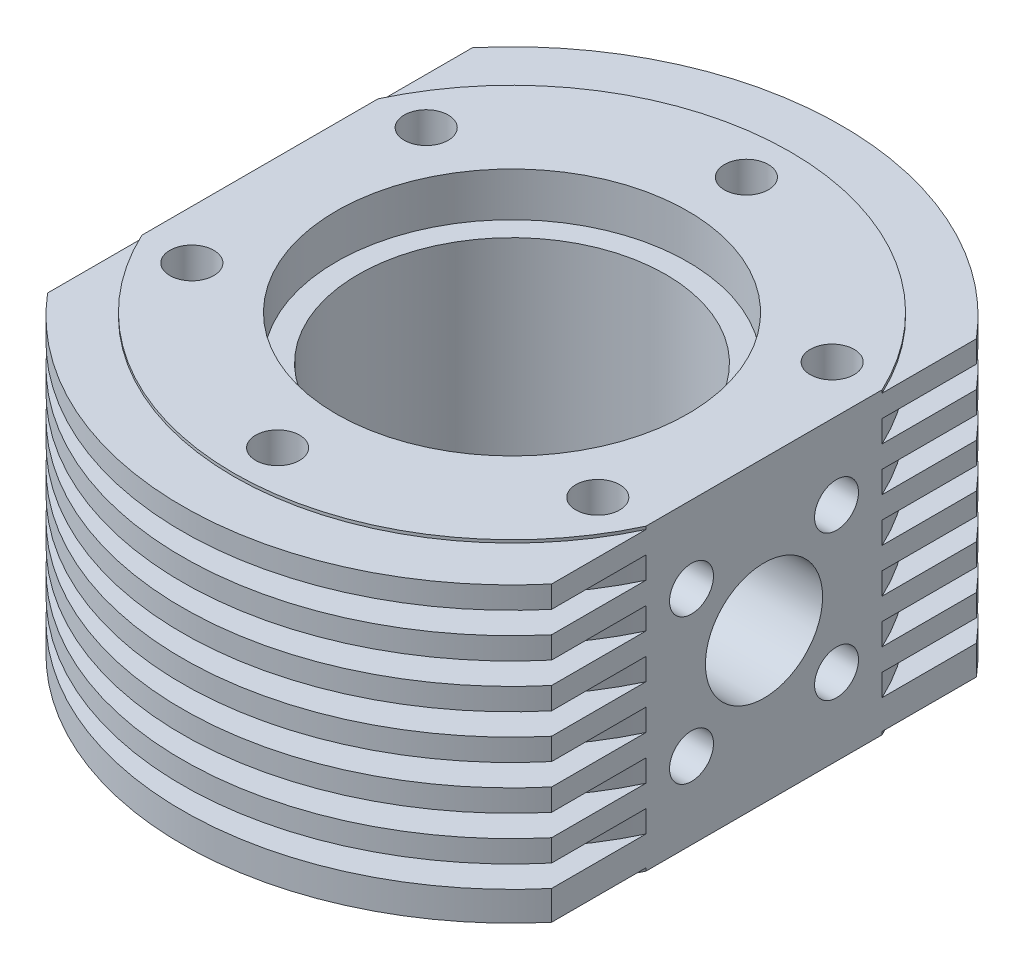
SolidWorks part; units mm, degrees
ref_plane "Front Plane" through (0, 0, 0) normal (0, 0, 1) x (1, 0, 0)
ref_plane "Top Plane" through (0, 0, 0) normal (0, 1, 0) x (1, 0, 0)
ref_plane "Right Plane" through (0, 0, 0) normal (1, 0, 0) x (0, 0, -1)
sketch "Sketch1" plane through (0, 0, 0) normal (0, 1, 0) x (1, 0, 0)
  line L0 (-17.2047, 14.5) -> (-17.2047, -14.5)
  line L1 (0, 0) -> (0, 11.2586) construction
  line L2 (17.2047, 14.5) -> (17.2047, -14.5)
  arc A0 (-17.2047, -14.5) -> (17.2047, -14.5) centre (0, 0) ccw
  arc A1 (-17.2047, -8.0623) -> (17.2047, -8.0623) centre (0, 0) ccw
  circle A2 centre (0, 0) radius 16 construction
  circle A3 centre (0, 16) radius 1.5
  circle A4 centre (13.8564, 8) radius 1.5
  circle A5 centre (13.8564, -8) radius 1.5
  circle A6 centre (0, -16) radius 1.5
  circle A7 centre (-13.8564, -8) radius 1.5
  circle A8 centre (-13.8564, 8) radius 1.5
  arc A9 (17.2047, 8.0623) -> (-17.2047, 8.0623) centre (0, 0) ccw
  arc A10 (17.2047, 14.5) -> (-17.2047, 14.5) centre (0, 0) ccw
  point P19 (0, 0)
  dimension "D1" = 45
  dimension "D2" = 38
  dimension "D3" = 32
  dimension "D4" = 3
  dimension "D5" = 6
extrude "Boss-Extrude1" add sketch "Sketch1" along normal mid plane 20 contours L2 A10 L0 A9 | A1 L0 A0 L2 region at (0, 0, -22.1268) region at (0, 0, 19.3732)
extrude "Boss-Extrude2" add sketch "Sketch1<4>" along normal mid plane 20.4 contours L2 A9 L0 A1 A3 A4 A5 A6 A7 A8 region at (0, 0, 0)
sketch "Sketch1<4>" plane through (0, 0, 0) normal (0, 1, 0) x (1, 0, 0) same geometry as "Sketch1"
sketch "Sketch2" plane through (0, 10.2, 0) normal (0, 1, 0) x (1, 0, 0)
  circle A0 centre (0, 0) radius 12
  circle A1 centre (0, 0) radius 10.5
  dimension "D1" = 24
  dimension "D2" = 21
extrude "Cut-Extrude1" cut sketch "Sketch2" against normal through all contours A1 region at (0, 10.2, 0)
extrude "Cut-Extrude2" cut sketch "Sketch2<3>" against normal blind 3 contours A0
sketch "Sketch2<3>" plane through (0, 10.2, 0) normal (0, 1, 0) x (1, 0, 0) same geometry as "Sketch2"
ref_plane "Plane1" through (0, 8.5, 0) normal (0, 1, 0) x (1, 0, 0)
sketch "Sketch3" plane through (0, 8.5, 0) normal (0, 1, 0) x (1, 0, 0)
  line L2 (17.2047, 8.0623) -> (17.2047, 14.5)
  line L3 (-17.2047, 14.5) -> (-17.2047, 8.0623)
  line L4 (17.2047, 8.0623) -> (17.2047, 14.5)
  line L5 (-17.2047, 14.5) -> (-17.2047, 8.0623)
  arc A2 (17.2047, 14.5) -> (-17.2047, 14.5) centre (0, 0) ccw
  arc A3 (17.2047, 8.0623) -> (-17.2047, 8.0623) centre (0, 0) ccw
  arc A4 (17.2047, 14.5) -> (-17.2047, 14.5) centre (0, 0) ccw
  arc A5 (17.2047, 8.0623) -> (-17.2047, 8.0623) centre (0, 0) ccw
  dimension "D1" = 0
extrude "Cut-Extrude3" cut sketch "Sketch3" against normal blind 1.5
pattern_linear "LPattern2" count 6 spacing 3 along (0, -1, 0) of "Cut-Extrude3"
mirror "Mirror1" about plane through (0, 0, 0) normal (0, 0, 1) of "LPattern2"
sketch "Sketch4" plane through (17.2047, 0, 0) normal (1, 0, 0) x (0, 0, -1)
  circle A0 centre (0, 0) radius 4
  dimension "D1" = 8
extrude "Cut-Extrude4" cut sketch "Sketch4" against normal up to next
sketch "Sketch5" plane through (17.2047, 0, 0) normal (1, 0, 0) x (0, 0, -1)
  line L0 (0, 7) -> (0, 0) construction
  line L1 (0, 0) -> (4.9497, 4.9497) construction
  circle A0 centre (0, 0) radius 7 construction
  circle A1 centre (4.9497, 4.9497) radius 1.5
  circle A2 centre (4.9497, -4.9497) radius 1.5
  circle A3 centre (-4.9497, -4.9497) radius 1.5
  circle A4 centre (-4.9497, 4.9497) radius 1.5
  point P15 (0, 0)
  dimension "D1" = 14
  dimension "D3" = 3
  dimension "D2" = 45
  dimension "D4" = 4
extrude "Cut-Extrude5" cut sketch "Sketch5" against normal blind 4
ref_plane "Plane2" through (0, 0.2, 0) normal (0, 1, 0) x (1, 0, 0)
sketch "Sketch6" plane through (0, 0.2, 0) normal (0, 1, 0) x (1, 0, 0)
  line L0 (-17.2047, -3) -> (-14.7047, -3)
  line L1 (-17.2047, 8.0623) -> (-17.2047, -8.0623) construction
  line L2 (-14.7047, -3) -> (-11.7047, 0)
  line L3 (-11.7047, 0) -> (-17.2047, 0)
  line L4 (-17.2047, 0) -> (-17.2047, -3)
  dimension "D1" = 45
  dimension "D2" = 3
  dimension "D3" = 2.5
revolve "Cut-Revolve1" cut sketch "Sketch6" angle 360 about L3
mirror "Mirror2" about plane through (0, 0, 0) normal (1, 0, 0) of "Cut-Extrude5"
